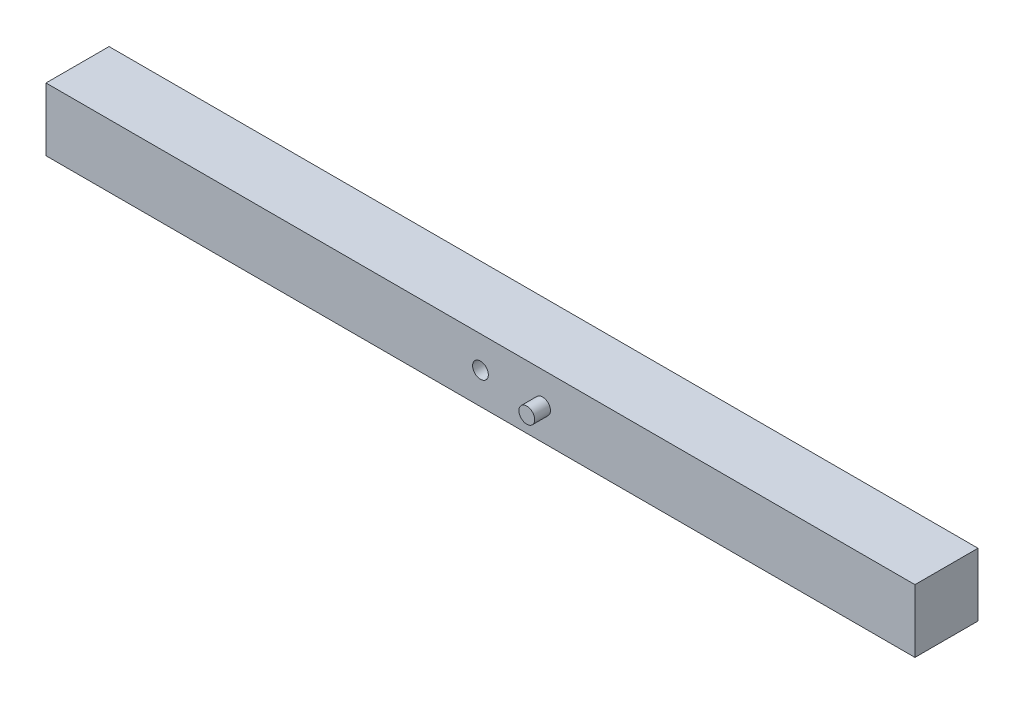
SolidWorks part; units mm, degrees
ref_plane "Front Plane" through (0, 0, 0) normal (0, 0, 1) x (1, 0, 0)
ref_plane "Top Plane" through (0, 0, 0) normal (0, 1, 0) x (1, 0, 0)
ref_plane "Right Plane" through (0, 0, 0) normal (1, 0, 0) x (0, 0, -1)
sketch "Sketch1" plane through (0, 0, 0) normal (0, 0, 1) x (1, 0, 0)
  line L0 (-40.2875, -8.0591) -> (659.7125, -8.0591) construction
  line L1 (-40.2875, 17.3409) -> (659.7125, 17.3409)
  line L2 (-40.2875, 17.3409) -> (-40.2875, -33.4591)
  line L3 (-40.2875, -33.4591) -> (659.7125, -33.4591)
  line L4 (659.7125, 17.3409) -> (659.7125, -33.4591)
  line L5 (309.7125, 17.3409) -> (309.7125, -33.4591) construction
  circle A0 centre (309.7125, -8.0591) radius 6.35
  dimension "D3" = 12.7
  dimension "D1" = 700
  dimension "D2" = 50.8
extrude "Boss-Extrude1" add sketch "Sketch1" along normal blind 50.8
sketch "Sketch2" plane through (0, 0, 50.8) normal (0, 0, 1) x (1, 0, 0)
  circle A0 centre (359.7125, -8.0591) radius 6.35
  circle A1 centre (309.7125, -8.0591) radius 6.35 construction
  point P5 (196.7685, 40.7302)
  dimension "D1" = 12.7
  dimension "D2" = 50
  dimension "D3" = 0
extrude "Boss-Extrude2" add sketch "Sketch2" along normal blind 12.7
